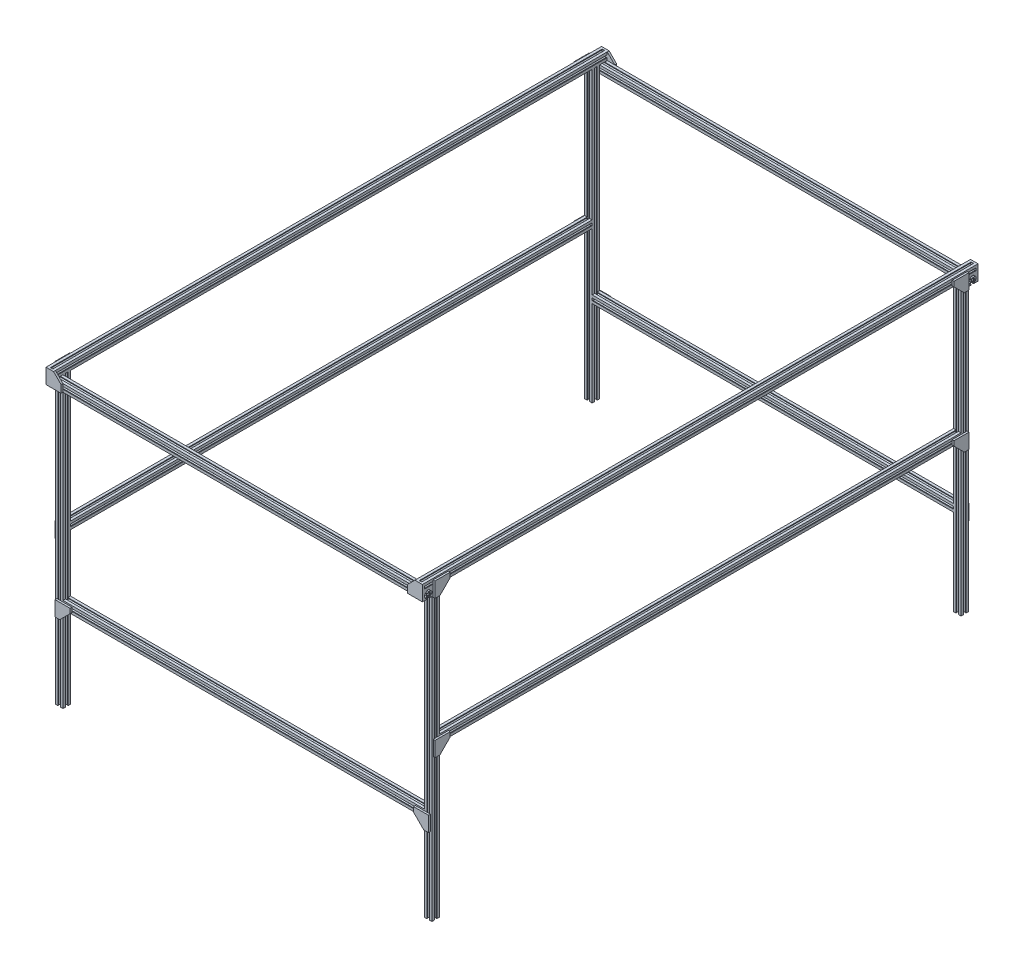
SolidWorks part; units mm, degrees
ref_plane "Front Plane" through (0, 0, 0) normal (0, 0, 1) x (1, 0, 0)
ref_plane "Top Plane" through (0, 0, 0) normal (0, 1, 0) x (1, 0, 0)
ref_plane "Right Plane" through (0, 0, 0) normal (1, 0, 0) x (0, 0, -1)
sketch "Sketch1" plane through (0, 0, 0) normal (0, 1, 0) x (1, 0, 0)
  line L100 (0, 0) -> (-28.059, 28.059) construction
  line L101 (-20, 0) -> (-13.2, 0)
  line L102 (-20, 0) -> (-20, 6.8)
  line L103 (-20, 20) -> (-13.2, 20)
  line L104 (0, 0) -> (0, 6.8)
  line L105 (-13.2, 20) -> (-13.2, 18.2)
  line L106 (0, 20) -> (-11.7678, 8.2322) construction
  line L107 (-7.05, 6.1) -> (-12.95, 6.1)
  line L108 (-6.1, 7.05) -> (-6.1, 12.95)
  line L109 (-7.05, 13.9) -> (-12.95, 13.9)
  line L110 (-13.9, 7.05) -> (-13.9, 12.95)
  line L111 (-6.1, 6.1) -> (-13.9, 13.9) construction
  line L112 (-6.1, 13.9) -> (-13.9, 6.1) construction
  line L113 (-15.45, 16.4) -> (-12.95, 13.9)
  line L114 (-6.8, 18.2) -> (-6.8, 20)
  line L115 (-18.2, 6.8) -> (-20, 6.8)
  line L116 (-20, 13.2) -> (-20, 20)
  line L117 (-20, 13.2) -> (-18.2, 13.2)
  line L118 (-10, 10) -> (-10, 13.9) construction
  line L119 (-3.6, 4.55) -> (-6.1, 7.05)
  line L120 (-15.45, 16.4) -> (-15.45, 18.2)
  line L121 (-15.45, 18.2) -> (-13.2, 18.2)
  line L122 (-6.8, 18.2) -> (-4.55, 18.2)
  line L123 (-4.55, 18.2) -> (-4.55, 16.4)
  line L124 (-4.55, 16.4) -> (-7.05, 13.9)
  line L125 (-3.6, 4.55) -> (-1.8, 4.55)
  line L126 (-1.8, 4.55) -> (-1.8, 6.8)
  line L127 (0, 6.8) -> (-1.8, 6.8)
  line L128 (-1.8, 13.2) -> (0, 13.2)
  line L129 (-1.8, 13.2) -> (-1.8, 15.45)
  line L130 (-1.8, 15.45) -> (-3.6, 15.45)
  line L131 (-3.6, 15.45) -> (-6.1, 12.95)
  line L132 (-18.2, 4.55) -> (-16.4, 4.55)
  line L133 (-16.4, 15.45) -> (-13.9, 12.95)
  line L134 (-16.4, 15.45) -> (-18.2, 15.45)
  line L135 (-18.2, 15.45) -> (-18.2, 13.2)
  line L136 (-20, 13.2) -> (-18.2, 13.2)
  line L137 (-18.2, 6.8) -> (-20, 6.8)
  line L138 (-16.4, 4.55) -> (-13.9, 7.05)
  line L139 (-18.2, 6.8) -> (-18.2, 4.55)
  line L140 (-4.55, 3.6) -> (-7.05, 6.1)
  line L141 (-15.45, 3.6) -> (-12.95, 6.1)
  line L142 (-15.45, 1.8) -> (-15.45, 3.6)
  line L143 (-13.2, 1.8) -> (-15.45, 1.8)
  line L144 (-13.2, 1.8) -> (-13.2, 0)
  line L145 (-4.55, 3.6) -> (-4.55, 1.8)
  line L146 (-4.55, 1.8) -> (-6.8, 1.8)
  line L147 (-6.8, 0) -> (-6.8, 1.8)
  line L148 (-6.8, 20) -> (0, 20)
  line L149 (0, 13.2) -> (0, 20)
  line L150 (-6.8, 0) -> (0, 0)
  line L151 (-13.9, 6.1) -> (-25.5045, -5.5045) construction
  circle A1 centre (-10, 10) radius 2.5
  point P140 (-10, 16.4)
  point P154 (-6.8, 19.1)
  point P161 (-19.1, 6.8)
  dimension "D13" = 5
  dimension "D12" = 20
  dimension "D14" = 7.8
  dimension "D15" = 7.8
  dimension "D16" = 6.8
  dimension "D17" = 6.8
  dimension "D18" = 1.8
  dimension "D19" = 10.9
  dimension "D20" = 1.8
  dimension "D21" = 10.9
  dimension "D22" = 20
extrude "Vertical Leg" add sketch "Sketch1" along normal blind 767.075 contours L147 L150 L104 L127 L126 L125 L119 L108 L131 L130 L129 L128 L149 L148 L114 L122 L123 L124 L109 L113 L120 L121 L105 L103 L116 L117 L135 L134 L133 L110 L138 L132 L139 L115 L102 L101 L144 L143 L142 L141 L107 L140 L145 L146 A1 region at (-19.7172, 0, -3.4)
sketch "Sketch2" plane through (-20, 0, 0) normal (-1, 0, 0) x (0, 0, 1)
  line L0 (0, 228.6) -> (-28.059, 256.659) construction
  line L1 (-20, 228.6) -> (-13.2, 228.6)
  line L2 (-20, 228.6) -> (-20, 235.4)
  line L3 (-20, 248.6) -> (-13.2, 248.6)
  line L4 (0, 228.6) -> (0, 235.4)
  line L5 (-13.2, 248.6) -> (-13.2, 246.8)
  line L6 (0, 248.6) -> (-11.7678, 236.8322) construction
  line L7 (-7.05, 234.7) -> (-12.95, 234.7)
  line L8 (-6.1, 235.65) -> (-6.1, 241.55)
  line L9 (-7.05, 242.5) -> (-12.95, 242.5)
  line L10 (-13.9, 235.65) -> (-13.9, 241.55)
  line L11 (-6.1, 234.7) -> (-13.9, 242.5) construction
  line L12 (-6.1, 242.5) -> (-13.9, 234.7) construction
  line L13 (-15.45, 245) -> (-12.95, 242.5)
  line L14 (-6.8, 246.8) -> (-6.8, 248.6)
  line L15 (-18.2, 235.4) -> (-20, 235.4)
  line L16 (-20, 241.8) -> (-20, 248.6)
  line L17 (-20, 241.8) -> (-18.2, 241.8)
  line L18 (-10, 238.6) -> (-10, 242.5) construction
  line L19 (-3.6, 233.15) -> (-6.1, 235.65)
  line L20 (-15.45, 245) -> (-15.45, 246.8)
  line L21 (-15.45, 246.8) -> (-13.2, 246.8)
  line L22 (-6.8, 246.8) -> (-4.55, 246.8)
  line L23 (-4.55, 246.8) -> (-4.55, 245)
  line L24 (-4.55, 245) -> (-7.05, 242.5)
  line L25 (-3.6, 233.15) -> (-1.8, 233.15)
  line L26 (-1.8, 233.15) -> (-1.8, 235.4)
  line L27 (0, 235.4) -> (-1.8, 235.4)
  line L28 (-1.8, 241.8) -> (0, 241.8)
  line L29 (-1.8, 241.8) -> (-1.8, 244.05)
  line L30 (-1.8, 244.05) -> (-3.6, 244.05)
  line L31 (-3.6, 244.05) -> (-6.1, 241.55)
  line L32 (-18.2, 233.15) -> (-16.4, 233.15)
  line L33 (-16.4, 244.05) -> (-13.9, 241.55)
  line L34 (-16.4, 244.05) -> (-18.2, 244.05)
  line L35 (-18.2, 244.05) -> (-18.2, 241.8)
  line L36 (-20, 241.8) -> (-18.2, 241.8)
  line L37 (-18.2, 235.4) -> (-20, 235.4)
  line L38 (-16.4, 233.15) -> (-13.9, 235.65)
  line L39 (-18.2, 235.4) -> (-18.2, 233.15)
  line L40 (-4.55, 232.2) -> (-7.05, 234.7)
  line L41 (-15.45, 232.2) -> (-12.95, 234.7)
  line L42 (-15.45, 230.4) -> (-15.45, 232.2)
  line L43 (-13.2, 230.4) -> (-15.45, 230.4)
  line L44 (-13.2, 230.4) -> (-13.2, 228.6)
  line L45 (-4.55, 232.2) -> (-4.55, 230.4)
  line L46 (-4.55, 230.4) -> (-6.8, 230.4)
  line L47 (-6.8, 228.6) -> (-6.8, 230.4)
  line L48 (-6.8, 248.6) -> (0, 248.6)
  line L49 (0, 241.8) -> (0, 248.6)
  line L50 (-6.8, 228.6) -> (0, 228.6)
  line L51 (-13.9, 234.7) -> (-25.5045, 223.0955) construction
  line L52 (-103.3225, 228.6) -> (77.3135, 228.6) construction
  line L53 (0, 0) -> (-6.8, 0) construction
  line L54 (20, 747.075) -> (-8.059, 775.134) construction
  line L55 (0, 747.075) -> (6.8, 747.075)
  line L56 (0, 747.075) -> (0, 753.875)
  line L57 (0, 767.075) -> (6.8, 767.075)
  line L58 (20, 747.075) -> (20, 753.875)
  line L59 (6.8, 767.075) -> (6.8, 765.275)
  line L60 (20, 767.075) -> (8.2322, 755.3072) construction
  line L61 (12.95, 753.175) -> (7.05, 753.175)
  line L62 (13.9, 754.125) -> (13.9, 760.025)
  line L63 (12.95, 760.975) -> (7.05, 760.975)
  line L64 (6.1, 754.125) -> (6.1, 760.025)
  line L65 (13.9, 753.175) -> (6.1, 760.975) construction
  line L66 (13.9, 760.975) -> (6.1, 753.175) construction
  line L67 (4.55, 763.475) -> (7.05, 760.975)
  line L68 (13.2, 765.275) -> (13.2, 767.075)
  line L69 (1.8, 753.875) -> (0, 753.875)
  line L70 (0, 760.275) -> (0, 767.075)
  line L71 (0, 760.275) -> (1.8, 760.275)
  line L72 (10, 757.075) -> (10, 760.975) construction
  line L73 (16.4, 751.625) -> (13.9, 754.125)
  line L74 (4.55, 763.475) -> (4.55, 765.275)
  line L75 (4.55, 765.275) -> (6.8, 765.275)
  line L76 (13.2, 765.275) -> (15.45, 765.275)
  line L77 (15.45, 765.275) -> (15.45, 763.475)
  line L78 (15.45, 763.475) -> (12.95, 760.975)
  line L79 (16.4, 751.625) -> (18.2, 751.625)
  line L80 (18.2, 751.625) -> (18.2, 753.875)
  line L81 (20, 753.875) -> (18.2, 753.875)
  line L82 (18.2, 760.275) -> (20, 760.275)
  line L83 (18.2, 760.275) -> (18.2, 762.525)
  line L84 (18.2, 762.525) -> (16.4, 762.525)
  line L85 (16.4, 762.525) -> (13.9, 760.025)
  line L86 (1.8, 751.625) -> (3.6, 751.625)
  line L87 (3.6, 762.525) -> (6.1, 760.025)
  line L88 (3.6, 762.525) -> (1.8, 762.525)
  line L89 (1.8, 762.525) -> (1.8, 760.275)
  line L90 (0, 760.275) -> (1.8, 760.275)
  line L91 (1.8, 753.875) -> (0, 753.875)
  line L92 (3.6, 751.625) -> (6.1, 754.125)
  line L93 (1.8, 753.875) -> (1.8, 751.625)
  line L94 (15.45, 750.675) -> (12.95, 753.175)
  line L95 (4.55, 750.675) -> (7.05, 753.175)
  line L96 (4.55, 748.875) -> (4.55, 750.675)
  line L97 (6.8, 748.875) -> (4.55, 748.875)
  line L98 (6.8, 748.875) -> (6.8, 747.075)
  line L99 (15.45, 750.675) -> (15.45, 748.875)
  line L100 (15.45, 748.875) -> (13.2, 748.875)
  line L101 (13.2, 747.075) -> (13.2, 748.875)
  line L102 (13.2, 767.075) -> (20, 767.075)
  line L103 (20, 760.275) -> (20, 767.075)
  line L104 (13.2, 747.075) -> (20, 747.075)
  line L105 (6.1, 753.175) -> (-5.5045, 741.5705) construction
  circle A0 centre (-10, 238.6) radius 2.5
  circle A1 centre (10, 757.075) radius 2.5
  point P23 (-10, 245)
  point P44 (-19.1, 235.4)
  point P84 (10, 763.475)
  point P98 (13.2, 766.175)
  point P105 (0.9, 753.875)
  line M3 (-13.2, 0) -> (-13.2, 767.075)
  line M5 (-20, 767.075) -> (-20, 0)
  dimension "D2" = 5
  dimension "D14" = 5
  dimension "D1" = 20
  dimension "D3" = 7.8
  dimension "D4" = 7.8
  dimension "D5" = 6.8
  dimension "D6" = 6.8
  dimension "D7" = 1.8
  dimension "D8" = 10.9
  dimension "D9" = 1.8
  dimension "D10" = 10.9
  dimension "D11" = 20
  dimension "D12" = 228.6
  dimension "D13" = 20
  dimension "D15" = 7.8
  dimension "D16" = 7.8
  dimension "D17" = 6.8
  dimension "D18" = 6.8
  dimension "D19" = 1.8
  dimension "D20" = 10.9
  dimension "D21" = 1.8
  dimension "D22" = 10.9
  dimension "D23" = 20
extrude "Short Horizontal" add sketch "Sketch2" along normal blind 479.425 contours L47 L50 L4 L27 L26 L25 L19 L8 L31 L30 L29 L28 L49 L48 L14 L22 L23 L24 L9 L13 L41 L7 L40 L45 L46 A0 M3 | L43 L42 L41 L13 L20 L21 L3 L17 L35 L34 L33 L10 L38 L32 L39 L15 L1 M3 M5 | L101 L104 L58 L81 L80 L79 L73 L62 L85 L84 L83 L82 L103 L102 L68 L76 L77 L78 L63 L67 L74 L75 L59 L57 L70 L71 L89 L88 L87 L64 L92 L86 L93 L69 L56 L55 L98 L97 L96 L95 L61 L94 L99 L100 A1 region at (-20, 232, -19.7888) region at (-20, 238.6, -12.9604) region at (-20, 750.475, 0.2828)
sketch "Sketch3" plane through (0, 0, -20) normal (0, 0, -1) x (-1, 0, 0)
  line L0 (-37.0014, 401) -> (61.5382, 401) construction
  line L1 (499.425, 248.6) -> (20, 248.6) construction
  line L2 (-37.0014, 421) -> (61.5382, 421) construction
  line L3 (-37.0014, 767.075) -> (61.5382, 767.075) construction
  line L4 (20, 401) -> (-8.059, 429.059) construction
  line L5 (0, 401) -> (6.8, 401)
  line L6 (0, 401) -> (0, 407.8)
  line L7 (0, 421) -> (6.8, 421)
  line L8 (20, 401) -> (20, 407.8)
  line L9 (6.8, 421) -> (6.8, 419.2)
  line L10 (20, 421) -> (8.2322, 409.2322) construction
  line L11 (12.95, 407.1) -> (7.05, 407.1)
  line L12 (13.9, 408.05) -> (13.9, 413.95)
  line L13 (12.95, 414.9) -> (7.05, 414.9)
  line L14 (6.1, 408.05) -> (6.1, 413.95)
  line L15 (13.9, 407.1) -> (6.1, 414.9) construction
  line L16 (13.9, 414.9) -> (6.1, 407.1) construction
  line L17 (4.55, 417.4) -> (7.05, 414.9)
  line L18 (13.2, 419.2) -> (13.2, 421)
  line L19 (1.8, 407.8) -> (0, 407.8)
  line L20 (0, 414.2) -> (0, 421)
  line L21 (0, 414.2) -> (1.8, 414.2)
  line L22 (10, 411) -> (10, 414.9) construction
  line L23 (16.4, 405.55) -> (13.9, 408.05)
  line L24 (4.55, 417.4) -> (4.55, 419.2)
  line L25 (4.55, 419.2) -> (6.8, 419.2)
  line L26 (13.2, 419.2) -> (15.45, 419.2)
  line L27 (15.45, 419.2) -> (15.45, 417.4)
  line L28 (15.45, 417.4) -> (12.95, 414.9)
  line L29 (16.4, 405.55) -> (18.2, 405.55)
  line L30 (18.2, 405.55) -> (18.2, 407.8)
  line L31 (20, 407.8) -> (18.2, 407.8)
  line L32 (18.2, 414.2) -> (20, 414.2)
  line L33 (18.2, 414.2) -> (18.2, 416.45)
  line L34 (18.2, 416.45) -> (16.4, 416.45)
  line L35 (16.4, 416.45) -> (13.9, 413.95)
  line L36 (1.8, 405.55) -> (3.6, 405.55)
  line L37 (3.6, 416.45) -> (6.1, 413.95)
  line L38 (3.6, 416.45) -> (1.8, 416.45)
  line L39 (1.8, 416.45) -> (1.8, 414.2)
  line L40 (0, 414.2) -> (1.8, 414.2)
  line L41 (1.8, 407.8) -> (0, 407.8)
  line L42 (3.6, 405.55) -> (6.1, 408.05)
  line L43 (1.8, 407.8) -> (1.8, 405.55)
  line L44 (15.45, 404.6) -> (12.95, 407.1)
  line L45 (4.55, 404.6) -> (7.05, 407.1)
  line L46 (4.55, 402.8) -> (4.55, 404.6)
  line L47 (6.8, 402.8) -> (4.55, 402.8)
  line L48 (6.8, 402.8) -> (6.8, 401)
  line L49 (15.45, 404.6) -> (15.45, 402.8)
  line L50 (15.45, 402.8) -> (13.2, 402.8)
  line L51 (13.2, 401) -> (13.2, 402.8)
  line L52 (13.2, 421) -> (20, 421)
  line L53 (20, 414.2) -> (20, 421)
  line L54 (13.2, 401) -> (20, 401)
  line L55 (6.1, 407.1) -> (-5.5045, 395.4955) construction
  line L56 (20, 767.075) -> (-8.059, 795.134) construction
  line L57 (0, 767.075) -> (6.8, 767.075)
  line L58 (0, 767.075) -> (0, 773.875)
  line L59 (0, 787.075) -> (6.8, 787.075)
  line L60 (20, 767.075) -> (20, 773.875)
  line L61 (6.8, 787.075) -> (6.8, 785.275)
  line L62 (20, 787.075) -> (8.2322, 775.3072) construction
  line L63 (12.95, 773.175) -> (7.05, 773.175)
  line L64 (13.9, 774.125) -> (13.9, 780.025)
  line L65 (12.95, 780.975) -> (7.05, 780.975)
  line L66 (6.1, 774.125) -> (6.1, 780.025)
  line L67 (13.9, 773.175) -> (6.1, 780.975) construction
  line L68 (13.9, 780.975) -> (6.1, 773.175) construction
  line L69 (4.55, 783.475) -> (7.05, 780.975)
  line L70 (13.2, 785.275) -> (13.2, 787.075)
  line L71 (1.8, 773.875) -> (0, 773.875)
  line L72 (0, 780.275) -> (0, 787.075)
  line L73 (0, 780.275) -> (1.8, 780.275)
  line L74 (10, 777.075) -> (10, 780.975) construction
  line L75 (16.4, 771.625) -> (13.9, 774.125)
  line L76 (4.55, 783.475) -> (4.55, 785.275)
  line L77 (4.55, 785.275) -> (6.8, 785.275)
  line L78 (13.2, 785.275) -> (15.45, 785.275)
  line L79 (15.45, 785.275) -> (15.45, 783.475)
  line L80 (15.45, 783.475) -> (12.95, 780.975)
  line L81 (16.4, 771.625) -> (18.2, 771.625)
  line L82 (18.2, 771.625) -> (18.2, 773.875)
  line L83 (20, 773.875) -> (18.2, 773.875)
  line L84 (18.2, 780.275) -> (20, 780.275)
  line L85 (18.2, 780.275) -> (18.2, 782.525)
  line L86 (18.2, 782.525) -> (16.4, 782.525)
  line L87 (16.4, 782.525) -> (13.9, 780.025)
  line L88 (1.8, 771.625) -> (3.6, 771.625)
  line L89 (3.6, 782.525) -> (6.1, 780.025)
  line L90 (3.6, 782.525) -> (1.8, 782.525)
  line L91 (1.8, 782.525) -> (1.8, 780.275)
  line L92 (0, 780.275) -> (1.8, 780.275)
  line L93 (1.8, 773.875) -> (0, 773.875)
  line L94 (3.6, 771.625) -> (6.1, 774.125)
  line L95 (1.8, 773.875) -> (1.8, 771.625)
  line L96 (15.45, 770.675) -> (12.95, 773.175)
  line L97 (4.55, 770.675) -> (7.05, 773.175)
  line L98 (4.55, 768.875) -> (4.55, 770.675)
  line L99 (6.8, 768.875) -> (4.55, 768.875)
  line L100 (6.8, 768.875) -> (6.8, 767.075)
  line L101 (15.45, 770.675) -> (15.45, 768.875)
  line L102 (15.45, 768.875) -> (13.2, 768.875)
  line L103 (13.2, 767.075) -> (13.2, 768.875)
  line L104 (13.2, 787.075) -> (20, 787.075)
  line L105 (20, 780.275) -> (20, 787.075)
  line L106 (13.2, 767.075) -> (20, 767.075)
  line L107 (6.1, 773.175) -> (-5.5045, 761.5705) construction
  line L108 (6.8, 0) -> (0, 0) construction
  circle A0 centre (10, 411) radius 2.5
  circle A1 centre (10, 777.075) radius 2.5
  point P31 (10, 417.4)
  point P52 (0.9, 407.8)
  point P88 (10, 783.475)
  point P102 (13.2, 786.175)
  point P109 (0.9, 773.875)
  line M13 (20, 248.6) -> (20, 767.075)
  line M14 (20, 767.075) -> (13.2, 767.075)
  line M15 (13.2, 767.075) -> (13.2, 0)
  dimension "D5" = 5
  dimension "D16" = 5
  dimension "D1" = 152.4
  dimension "D2" = 20
  dimension "D3" = 346.075
  dimension "D4" = 20
  dimension "D6" = 7.8
  dimension "D7" = 7.8
  dimension "D8" = 6.8
  dimension "D9" = 6.8
  dimension "D10" = 1.8
  dimension "D11" = 10.9
  dimension "D12" = 1.8
  dimension "D13" = 10.9
  dimension "D14" = 20
  dimension "D15" = 20
  dimension "D17" = 7.8
  dimension "D18" = 7.8
  dimension "D19" = 6.8
  dimension "D20" = 6.8
  dimension "D21" = 1.8
  dimension "D22" = 10.9
  dimension "D23" = 1.8
  dimension "D24" = 10.9
  dimension "D25" = 20
  dimension "D26" = 401
extrude "Long Horizontal" add sketch "Sketch3" along normal blind 692.15 contours L48 L47 L46 L45 L11 L44 L28 L13 L17 L24 L25 L9 L7 L20 L21 L39 L38 L37 L14 L42 L36 L43 L19 L6 L5 A0 M15 | L54 L31 L30 L29 L23 L12 L35 L34 L33 L32 L52 L26 L27 L28 L44 L49 L50 M15 M13 | L106 L83 L82 L81 L75 L64 L87 L86 L85 L84 L78 L79 L80 L96 L101 L102 M15 M13 M14 | L105 L104 L70 M14 | L100 L99 L98 L97 L63 L96 L80 L65 L69 L76 L77 L61 L59 L72 L73 L91 L90 L89 L66 L94 L88 L95 L71 L58 L57 A1 M15 region at (-0.2396, 404.4, -20) region at (-13.4112, 411, -20) region at (-13.4828, 767.975, -20)
extrude "Long Horizontal Backwards" add sketch "Sketch3<3>" against normal blind 40 contours L84 L105 L104 L70 L78 L79 L80 L65 L69 L76 L77 L61 L59 L72 L73 L91 L90 L89 L66 L94 L88 L95 L71 L58 L57 L100 L99 L98 L97 L63 L96 L101 L102 L103 L60 L83 L82 L81 L75 L64 L87 L86 L85 A1 M14 region at (-0.2828, 770.475, -20)
sketch "Sketch3<3>" plane through (0, 0, -20) normal (0, 0, -1) x (-1, 0, 0) same geometry as "Sketch3"
extrude "Short Horizontal Backwards" add sketch "Sketch2<3>" against normal blind 20 contours L101 L104 L58 L81 L80 L79 L73 L62 L85 L84 L83 L82 L103 L102 L68 L76 L77 L78 L63 L67 L74 L75 L59 L57 L70 L71 L89 L88 L87 L64 L92 L86 L93 L69 L56 L55 L98 L97 L96 L95 L61 L94 L99 L100 A1 region at (-20, 750.475, 0.2828)
sketch "Sketch2<3>" plane through (-20, 0, 0) normal (-1, 0, 0) x (0, 0, 1) same geometry as "Sketch2"
sketch "Sketch4" plane through (0, 0, 0) normal (1, 0, 0) x (0, 0, -1)
  line L0 (3.5094, 743.5656) -> (16.4906, 743.5656)
  line L1 (16.4906, 743.5656) -> (43.5094, 770.5844)
  line L2 (43.5094, 770.5844) -> (43.5094, 783.5656)
  line L3 (43.5094, 783.5656) -> (3.5094, 783.5656)
  line L4 (3.5094, 783.5656) -> (3.5094, 743.5656)
  line L5 (13.2, 767.075) -> (6.8, 767.075) construction
  line L6 (-20, 774.125) -> (-20, 780.025) construction
  line L7 (3.8545, 417.1455) -> (43.8545, 417.1455)
  line L8 (43.8545, 417.1455) -> (43.8545, 404.8545)
  line L9 (43.8545, 404.8545) -> (16.1455, 377.1455)
  line L10 (16.1455, 377.1455) -> (3.8545, 377.1455)
  line L11 (3.8545, 377.1455) -> (3.8545, 417.1455)
  line L12 (7.05, 0) -> (12.95, 0) construction
  line L13 (20, 414.2) -> (20, 407.8) construction
  point P7 (10, 743.5656)
  point P8 (10, 767.075)
  point P9 (-20, 777.075)
  point P12 (43.5094, 777.075)
  point P13 (43.5094, 770.5844)
  point P19 (3.7633, 419.1633)
  point P20 (32.3662, 395.9403)
  point P21 (-13.2193, 415.8811)
  point P22 (10, 377.1455)
  point P25 (10, 0)
  point P26 (43.8545, 411)
  point P29 (20, 411)
  point P30 (3.8545, 417.1455)
  dimension "D1" = 135
  dimension "D2" = 40
  dimension "D3" = 40
  dimension "D4" = 135
extrude "Brackets 1 & 2" add sketch "Sketch4" along normal blind 5
sketch "Sketch5" plane through (0, 0, 20) normal (0, 0, 1) x (1, 0, 0)
  line L0 (-40, 747.075) -> (-40, 767.075)
  line L1 (-40, 767.075) -> (-20, 787.075)
  line L2 (-20, 787.075) -> (0, 787.075)
  line L3 (0, 787.075) -> (0, 747.075)
  line L4 (0, 747.075) -> (-40, 747.075)
  line L5 (0, 754.125) -> (0, 760.025) construction
  line L6 (-12.95, 780.975) -> (-7.05, 780.975) construction
  point P7 (0, 757.075)
  point P8 (-40, 757.075)
  point P9 (-10, 787.075)
  point P12 (-10, 780.975)
  point P13 (-37.1272, 770.2335)
  point P14 (-39.0354, 762.3945)
  point P15 (-0.3407, 786.4978)
  point P16 (0, 787.075)
  dimension "D1" = 135
extrude "Bracket 3" add sketch "Sketch5" along normal blind 5
sketch "Sketch6" plane through (0, 0, 0) normal (0, 0, 1) x (1, 0, 0)
  line L0 (-43.6796, 244.9204) -> (-43.6796, 232.2796)
  line L1 (-43.6796, 232.2796) -> (-16.3204, 204.9204)
  line L2 (-16.3204, 204.9204) -> (-3.6796, 204.9204)
  line L3 (-3.6796, 204.9204) -> (-3.6796, 244.9204)
  line L4 (-3.6796, 244.9204) -> (-43.6796, 244.9204)
  line L5 (-20, 235.65) -> (-20, 241.55) construction
  line L6 (-7.05, 0) -> (-12.95, 0) construction
  point P7 (-20, 238.6)
  point P8 (-43.6796, 238.6)
  point P9 (-10, 204.9204)
  point P12 (-10, 0)
  point P13 (-45.4249, 244.2613)
  point P14 (-43.6796, 232.2796)
  dimension "D1" = 135
  dimension "D2" = 40
extrude "Bracket 4" add sketch "Sketch6" along normal blind 5
mirror "Mirror1" about plane through (0, 0, -712.15) normal (0, 0, -1) of bodies 114 103
mirror "Mirror2" about plane through (-499.425, 0, 0) normal (-1, 0, 0) of bodies 104
